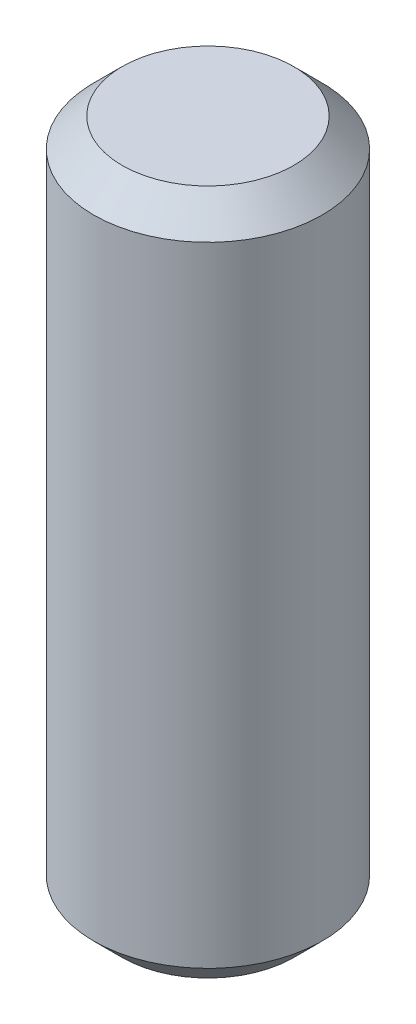
SolidWorks part; units mm, degrees
ref_plane "Front Plane" through (0, 0, 0) normal (0, 0, 1) x (1, 0, 0)
ref_plane "Top Plane" through (0, 0, 0) normal (0, 1, 0) x (1, 0, 0)
ref_plane "Right Plane" through (0, 0, 0) normal (1, 0, 0) x (0, 0, -1)
sketch "Sketch2" plane through (0, 0, 0) normal (0, 1, 0) x (1, 0, 0)
  circle A0 centre (0, 0) radius 2
  dimension "D1" = 4
extrude "Boss-Extrude1" add sketch "Sketch2" along normal blind 12
chamfer "Chamfer1" distance 0.5 angle 45 2 edges at (0, 0, 2) (0, 12, 2)
